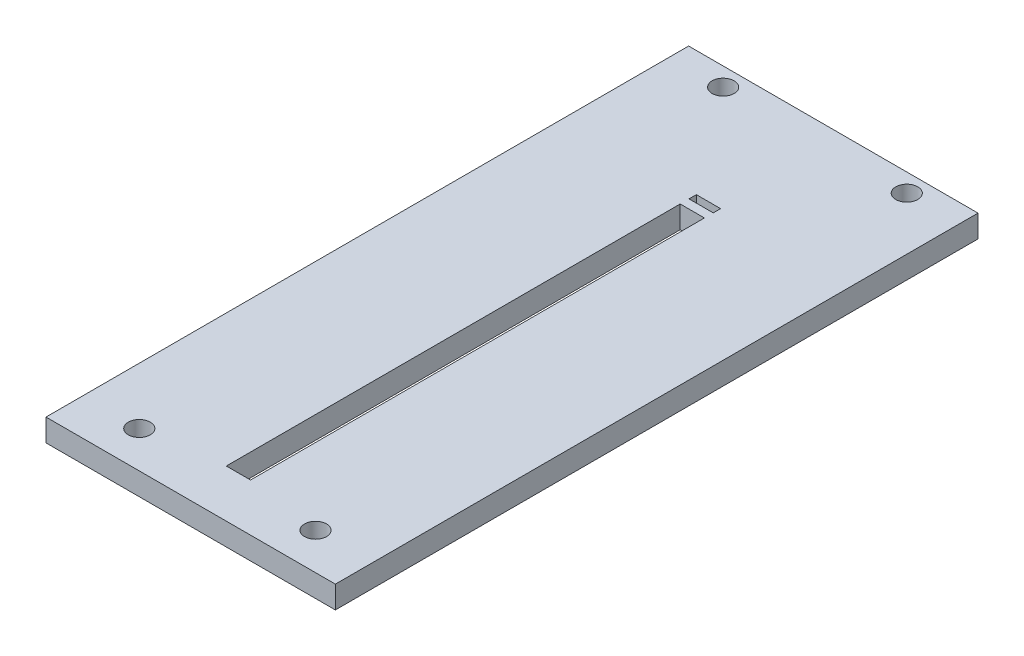
SolidWorks part; units mm, degrees
ref_plane "Front Plane" through (0, 0, 0) normal (0, 0, 1) x (1, 0, 0)
ref_plane "Top Plane" through (0, 0, 0) normal (0, 1, 0) x (1, 0, 0)
ref_plane "Right Plane" through (0, 0, 0) normal (1, 0, 0) x (0, 0, -1)
sketch "Sketch1" plane through (0, 0, 0) normal (0, 1, 0) x (1, 0, 0)
  line L1 (-19.7, 0) -> (19.7, 0)
  line L2 (-19.7, 0) -> (-19.7, 87.5)
  line L3 (-19.7, 87.5) -> (19.7, 87.5)
  line L4 (19.7, 0) -> (19.7, 87.5)
  point P5 (0, 0)
  dimension "D1" = 39.4
  dimension "D2" = 87.5
extrude "Boss-Extrude1" add sketch "Sketch1" along normal blind 3.05 contours L2 | L1 L4 L3 L2 | L4 region at (0, 0, -43.75)
sketch "Sketch4" plane through (0, 3.05, 0) normal (0, 1, 0) x (1, 0, 0)
  line L0 (-19.7, 87.5) -> (19.7, 87.5) construction
  line L2 (-19.7, 0) -> (19.7, 0) construction
  line L3 (1.65, 70.5) -> (-1.65, 70.5)
  line L4 (-1.65, 70.5) -> (-1.65, 69.5)
  line L5 (-1.65, 69.5) -> (1.65, 69.5)
  line L6 (1.65, 69.5) -> (1.65, 70.5)
  line L7 (0, 0) -> (0, 87.5) construction
  line L9 (1.65, 68.3) -> (-1.65, 68.3)
  line L10 (-1.65, 68.3) -> (-1.65, 6.5)
  line L11 (-1.65, 6.5) -> (1.65, 6.5)
  line L12 (1.65, 6.5) -> (1.65, 68.3)
  point P6 (0, 6.5)
  point P10 (0, 70.5)
  point P22 (0, 68.3)
  dimension "D1" = 17
  dimension "D2" = 1
  dimension "D3" = 1.2
  dimension "D4" = 3.3
  dimension "D7" = 6.5
extrude "Cut-Extrude1" cut sketch "Sketch4" against normal through all contours L5 L7 L3 L4 | L11 L7 L9 L10 | L7 L11 L12 L9 | L7 L5 L6 L3 | L6 L3 L4 L5 region at (0.825, 3.05, -70) region at (0.825, 3.05, -37.4) region at (-0.825, 3.05, -37.4) region at (-0.825, 3.05, -70)
sketch "Sketch7" plane through (0, 3.05, 0) normal (0, 1, 0) x (1, 0, 0)
  line L0 (0, 0) -> (-12, 0)
  line L1 (-19.7, 0) -> (19.7, 0) construction
  line L2 (-12, 0) -> (-12, 5)
  line L4 (0, 0) -> (0, 70) construction
  circle A0 centre (-12, 5) radius 1.5
  circle A2 centre (12, 5) radius 1.5
  dimension "D3" = 3
  dimension "D1" = 12
  dimension "D2" = 5
extrude "Cut-Extrude4" cut sketch "Sketch7" against normal through all contours A0 L2 | L2 A0 | A2 region at (-10.9693, 3.05, -3.9693)
hole_wizard "Ø3.0mm Dowel Hole1" positions "Sketch8" profile "Sketch9" hole size "Ø3.0" standard "ANSI Metric" end condition through all
sketch "Sketch8" plane through (0, 3.05, 0) normal (0, 1, 0) x (1, 0, 0)
  line L0 (0, 87.5332) -> (0, 2.5332) construction
  line L3 (-19.7, 87.5) -> (19.7, 87.5) construction
  point P0 (-12.5, 85)
  point P2 (12.5, 85)
  dimension "D1" = 12.5
  dimension "D2" = 2.5
sketch "Sketch9" plane through (-12.5, 3.05, -85) normal (1, 0, 0) x (0, 0, 1)
  line L0 (0, 0) -> (0, 3.05)
  line L1 (0, 3.05) -> (1.5, 3.05)
  line L2 (1.5, 3.05) -> (1.5, 0)
  line L5 (1.5, 0) -> (0, 0)
  line L11 (0, -6.35) -> (0, 107.95) construction
  dimension "Thru Hole Dia." = 3
  dimension "Thru Hole Depth" = 3.05
